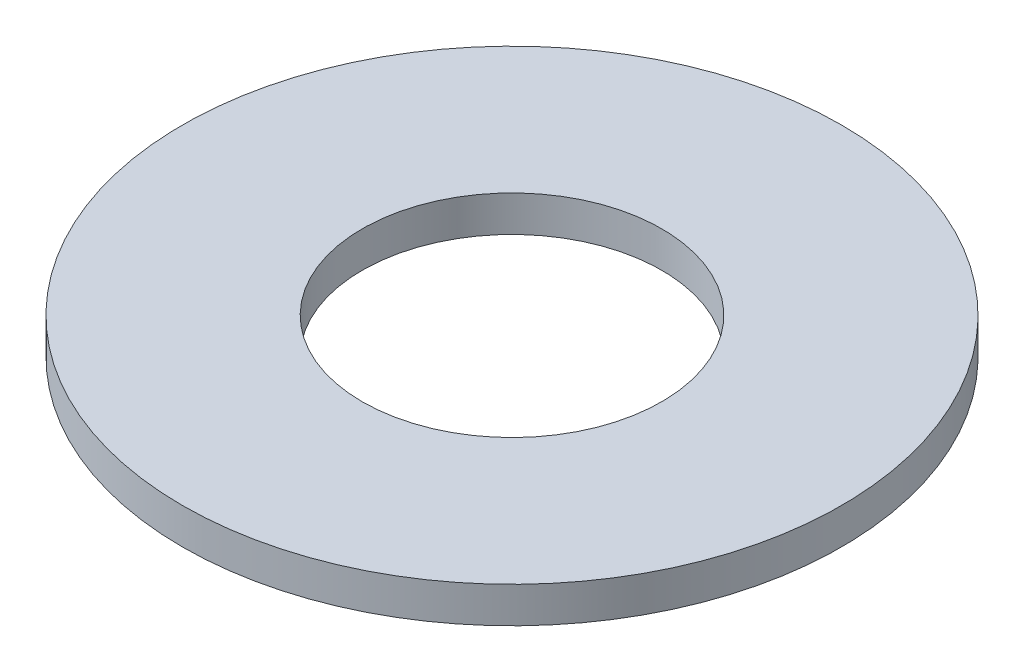
SolidWorks part; units mm, degrees
ref_plane "Front Plane" through (0, 0, 0) normal (0, 0, 1) x (1, 0, 0)
ref_plane "Top Plane" through (0, 0, 0) normal (0, 1, 0) x (1, 0, 0)
ref_plane "Right Plane" through (0, 0, 0) normal (1, 0, 0) x (0, 0, -1)
sketch "Sketch1" plane through (0, 0, 0) normal (0, 1, 0) x (1, 0, 0)
  circle A0 centre (0, 0) radius 82.5
  dimension "FLANGE_OD" = 165
extrude "Boss-Extrude1" add sketch "Sketch1" along normal blind 9
sketch "Sketch2" plane through (0, 0, 0) normal (0, 1, 0) x (1, 0, 0)
  circle A0 centre (0, 0) radius 37.5
  dimension "BORE_D" = 75
extrude "Cut-Extrude1" cut sketch "Sketch2" along normal through all
sketch "Sketch3" plane through (0, 9, 0) normal (0, 1, 0) x (1, 0, 0)
  circle A0 centre (0, 0) radius 25.3576 construction
  circle A1 centre (-25.3576, 0) radius 7.0027
  dimension "BOLT_D" = 14.0054
  dimension "BOLT_PCD" = 50.7153
extrude "Cut-Extrude2" cut sketch "Sketch3" against normal blind 6.6517 rebuild error yes
pattern_circular "CirPattern1" count 3 over 360 rebuild error yes
